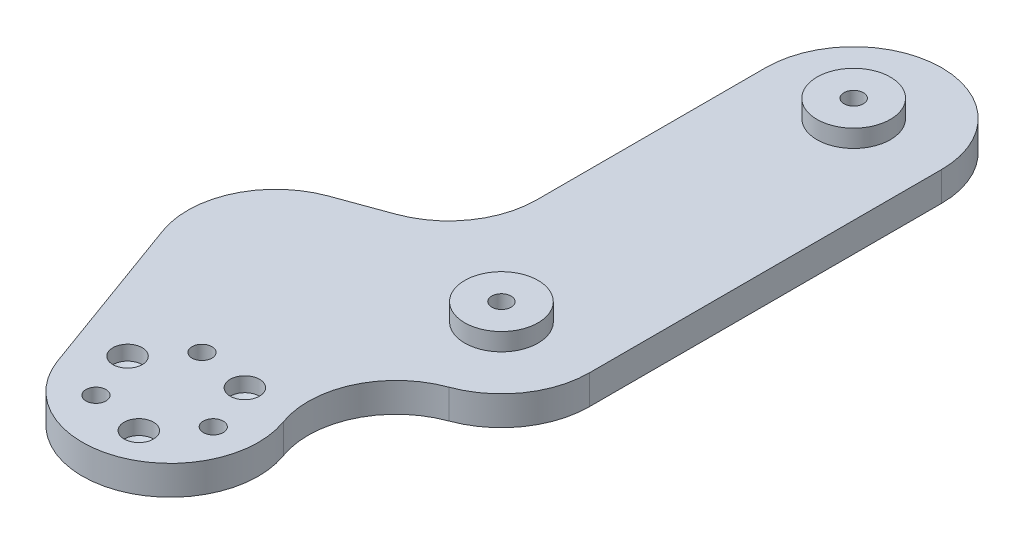
SolidWorks part; units mm, degrees
material "7075-T6 (SN)"
ref_plane "정면" through (0, 0, 0) normal (0, 0, 1) x (1, 0, 0)
ref_plane "윗면" through (0, 0, 0) normal (0, 1, 0) x (1, 0, 0)
ref_plane "우측면" through (0, 0, 0) normal (1, 0, 0) x (0, 0, -1)
sketch "스케치1" plane through (0, 0, 0) normal (0, 1, 0) x (1, 0, 0)
  line L0 (0, 0) -> (0, 60) construction
  line L2 (-15, 0) -> (-15, 60)
  line L3 (15, 0) -> (15, 60)
  arc A0 (-15, 0) -> (15, 0) centre (0, 0) ccw
  arc A1 (15, 60) -> (-15, 60) centre (0, 60) ccw
  point P5 (0, 30)
  dimension "D2" = 15
  dimension "D1" = 60
extrude "보스-돌출1" add sketch "스케치1" along normal blind 5
sketch "스케치2" plane through (0, 5, 0) normal (0, 1, 0) x (1, 0, 0)
  line L0 (0, 60) -> (0, 0) construction
  circle A0 centre (0, 60) radius 6.25
  circle A1 centre (0, 0) radius 6.25
  dimension "D2" = 12.5
  dimension "D3" = 12.5
  dimension "D1" = 60
extrude "보스-돌출2" add sketch "스케치2" along normal blind 3
hole_wizard "M4 탭을 위한 탭 드릴1" positions "스케치5" profile "스케치7" hole size "M4" standard "ISO"
sketch "스케치5" plane through (0, 8, 0) normal (0, 1, 0) x (1, 0, 0)
  point P0 (0, 0)
  point P3 (0, 60)
sketch "스케치7" plane through (0, 8, 0) normal (1, 0, 0) x (0, 0, 1)
  line L0 (0, 0) -> (0, 5.9914)
  line L1 (0, 5.9914) -> (1.65, 5)
  line L2 (1.65, 5) -> (1.65, 0)
  line L5 (1.65, 0) -> (0, 0)
  line L10 (0, 5.9914) -> (-1.65, 5) construction
  line L11 (0, -6.35) -> (0, 107.95) construction
  dimension "구멍 지름" = 3.3
  dimension "구멍 깊이" = 5
  dimension "드릴 각도" = 118
sketch "스케치9" plane through (0, 0, 0) normal (0, -1, 0) x (1, 0, 0)
  line L0 (0, 0) -> (-41.3824, 15.062) construction
  line L1 (-15, -60) -> (-15, 0) construction
  line L2 (0, 0) -> (-28.1908, 10.2606) construction
  line L3 (-5.1303, -14.0954) -> (-33.3211, -3.8348)
  line L4 (5.1303, 14.0954) -> (-23.0605, 24.356)
  arc A0 (-5.1303, -14.0954) -> (5.1303, 14.0954) centre (0, 0) ccw
  arc A1 (-23.0605, 24.356) -> (-33.3211, -3.8348) centre (-28.1908, 10.2606) ccw
  point P5 (-14.0954, 5.1303)
  dimension "D3" = 15
  dimension "D1" = 110
  dimension "D2" = 30
extrude "보스-돌출3" add sketch "스케치9" against normal blind 5
sketch "스케치10" plane through (0, 0, 0) normal (0, -1, 0) x (1, 0, 0)
  line L9 (-28.1908, 10.2606) -> (-17.9302, 38.4514) construction
  line L10 (-42.2862, 15.3909) -> (-32.0256, 43.5817)
  line L11 (-14.0954, 5.1303) -> (-3.8348, 33.3211)
  line L12 (5.1303, 14.0954) -> (-23.0605, 24.356) construction
  arc A5 (-42.2862, 15.3909) -> (-14.0954, 5.1303) centre (-28.1908, 10.2606) ccw
  arc A6 (-3.8348, 33.3211) -> (-32.0256, 43.5817) centre (-17.9302, 38.4514) ccw
  point P2 (-23.0605, 24.356)
  dimension "D2" = 15
  dimension "D4" = 90
  dimension "D1" = 30
extrude "보스-돌출4" add sketch "스케치10" against normal blind 5
sketch "스케치11" plane through (0, 0, 0) normal (0, -1, 0) x (1, 0, 0)
  line L0 (-13.9506, 49.3853) -> (-22.2403, 26.6093) construction
  line L1 (-8.9651, 19.2257) -> (-3.8348, 33.3211) construction
  circle A0 centre (-17.9302, 38.4514) radius 9 construction
  dimension "D1" = 18
hole_wizard "M3 육각 소켓 머리 캡 나사용 카운터보어1" positions "스케치12" profile "스케치13" counterbore size "M3" standard "ISO" end condition through all
sketch "스케치12" plane through (0, 0, 0) normal (0, -1, 0) x (-1, 0, 0)
  line L0 (13.9506, -49.3853) -> (22.2403, -26.6093) construction
  circle A0 centre (17.9302, -38.4514) radius 9 construction
  point P0 (21.0084, -29.9941)
sketch "스케치13" plane through (-21.0084, 0, 29.9941) normal (1, 0, 0) x (0, 0, -1)
  line L0 (0, 0) -> (0, 8)
  line L1 (0, 8) -> (1.7, 8)
  line L3 (1.7, 8) -> (1.7, 2)
  line L4 (1.7, 2) -> (3.25, 2)
  line L5 (3.25, 2) -> (3.25, 0)
  line L7 (3.25, 0) -> (0, 0)
  line L11 (0, -6.35) -> (0, 107.95) construction
  dimension "관통 구멍 지름" = 3.4
  dimension "관통 구멍 깊이" = 8
  dimension "카운터보어 지름" = 6.5
  dimension "카운터보어 깊이" = 2
pattern_circular "원형 패턴2" count 3 over 360 about axis through (-17.9302, 5, 38.4514) along (0, -1, 0) of "M3 육각 소켓 머리 캡 나사용 카운터보어1"
hole_wizard "Ø5.0mm 맞춤핀 구멍1" positions "스케치16" profile "스케치18" hole size "Ø5.0" standard "ISO"
sketch "스케치16" plane through (0, 5, 0) normal (0, 1, 0) x (1, 0, 0)
  line L0 (-13.9506, -49.3853) -> (-22.2403, -26.6093) construction
  circle A0 centre (-17.9302, -38.4514) radius 9 construction
  point P0 (-14.852, -46.9086)
sketch "스케치18" plane through (-14.852, 5, 46.9086) normal (1, 0, 0) x (0, 0, 1)
  line L0 (0, 0) -> (0, 4.0022)
  line L1 (0, 4.0022) -> (2.5, 2.5)
  line L2 (2.5, 2.5) -> (2.5, 0)
  line L5 (2.5, 0) -> (0, 0)
  line L10 (0, 4.0022) -> (-2.5, 2.5) construction
  line L11 (0, -6.35) -> (0, 107.95) construction
  dimension "구멍 지름" = 5
  dimension "구멍 깊이" = 2.5
  dimension "드릴 각도" = 118
pattern_circular "원형 패턴3" count 3 over 360 about axis through (-17.9302, 5, 38.4514) along (0, -1, 0) of "Ø5.0mm 맞춤핀 구멍1" reverse direction yes
fillet "필렛1" radius 15 2 edges at (-8.9651, 2.5, 19.2257) (-15, 2.5, -10.5031)
